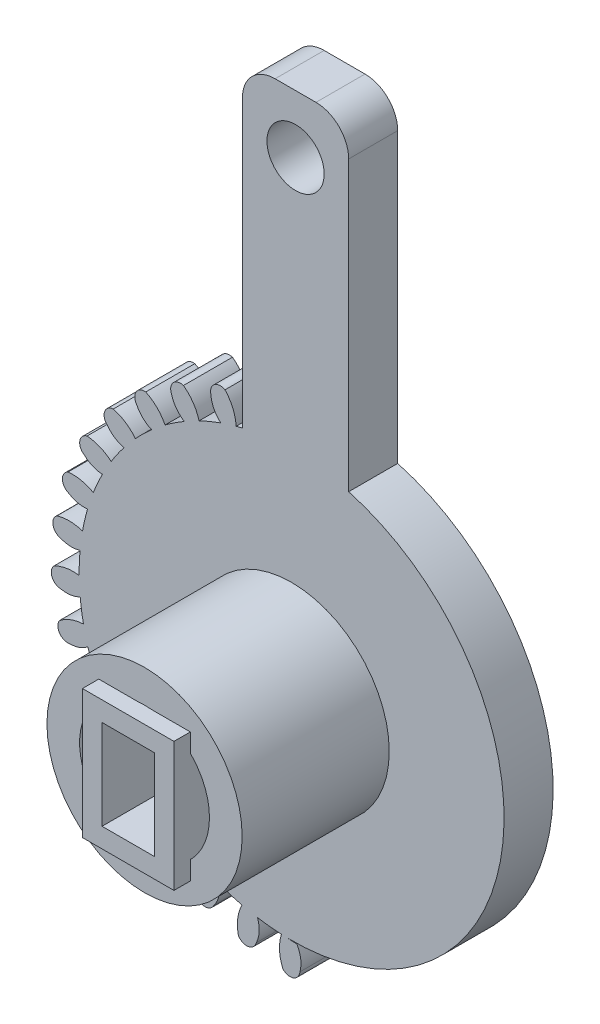
SolidWorks part; units mm, degrees
ref_plane "Front Plane" through (0, 0, 0) normal (0, 0, 1) x (1, 0, 0)
ref_plane "Top Plane" through (0, 0, 0) normal (0, 1, 0) x (1, 0, 0)
ref_plane "Right Plane" through (0, 0, 0) normal (1, 0, 0) x (0, 0, -1)
ref_plane "Plane1" through (0, 0, 5) normal (0, 0, 1) x (1, 0, 0)
ref_plane "Plane2" through (0, 0, 11) normal (0, 0, 1) x (1, 0, 0)
ref_plane "Plane3" through (0, 0, 3) normal (0, 0, 1) x (1, 0, 0)
sketch "Sketch1" plane through (0, 0, 5) normal (0, 0, 1) x (1, 0, 0)
  circle A0 centre (0, 20.9252) radius 3.9726
  circle A1 centre (0, 20.9252) radius 5
  dimension "D1" = 10
sketch "Sketch3" plane through (0, 0, 11) normal (0, 0, 1) x (1, 0, 0)
  line L0 (-3.9726, 20.9252) -> (15.3734, 20.9252) construction
  line L1 (0, 24.8978) -> (0, 8.7425) construction
  line L3 (-1.6, 23.6752) -> (1.6, 23.6752)
  line L4 (-1.6, 23.6752) -> (-1.6, 18.1752)
  line L5 (-1.6, 18.1752) -> (1.6, 18.1752)
  line L6 (1.6, 23.6752) -> (1.6, 18.1752)
  dimension "D1" = 3.2
  dimension "D2" = 5.5
  dimension "D3" = 1.6
  dimension "D4" = 2.75
extrude "Boss-Extrude1" add sketch "Sketch1" along normal blind 10 contours A0
shell "Shell1" thickness 2 removed face at (3.9726, 20.9252, 15) outward yes
extrude "Boss-Extrude2" add sketch "Sketch3" along normal blind 5 separate body
shell "Shell2" thickness 1.2 removed face at (0, 20.9252, 16) outward yes
sketch "Sketch7" plane through (0, 0, 3) normal (0, 0, -1) x (-1, 0, 0)
  line L0 (0, 14.9526) -> (0, 35.2199) construction
  line L1 (5.9726, 20.9252) -> (-26.894, 20.9252) construction
  circle A0 centre (0, 20.9252) radius 5.9726 construction
sketch "Sketch5" plane through (0, 0, 3) normal (0, 0, 1) x (1, 0, 0)
  line L1 (0, 14.9526) -> (0, 35.2199) construction
  line L2 (-5.9726, 20.9252) -> (26.894, 20.9252) construction
  circle A0 centre (0, 20.9252) radius 13
extrude "Boss-Extrude3" add sketch "Sketch5" along normal blind 3 contours A0
sketch "Sketch6" plane through (0, 0, 3) normal (0, 0, 1) x (1, 0, 0)
  line L1 (-3.01, 33.0817) -> (3.49, 33.0817)
  line L2 (-3.01, 33.0817) -> (-3.01, 53.0817)
  line L3 (-3.01, 53.0817) -> (3.49, 53.0817)
  line L4 (3.49, 33.0817) -> (3.49, 53.0817)
  point P4 (-3.01, 33.0817)
  dimension "D1" = 20
  dimension "D2" = 6.5
extrude "Boss-Extrude4" add sketch "Sketch6" along normal up to surface (3 mm away) up to face at (5.9726, 20.9252, 6)
sketch "Sketch8" plane through (0, 0, 3) normal (0, 0, 1) x (1, 0, 0)
  line L0 (-4.296, 33.1462) -> (-3.39, 33.4105)
  line L1 (0.24, 53.0817) -> (0.24, -3.388) construction
  line L2 (3.49, 53.0817) -> (-3.01, 53.0817) construction
  line L3 (13, 20.9252) -> (-7.0281, 20.9252) construction
  line L4 (-6.4797, 32.0955) -> (-5.6382, 32.5229)
  line L5 (-8.4311, 30.6587) -> (-7.6833, 31.2345)
  line L6 (-10.0829, 28.8855) -> (-9.4546, 29.5898)
  line L7 (-11.3779, 26.8373) -> (-10.8908, 27.6456)
  line L8 (-12.2715, 24.5847) -> (-11.9424, 25.4693)
  line L9 (-12.7326, 22.2057) -> (-12.573, 23.1358)
  line L10 (-12.7455, 19.7824) -> (-12.7607, 20.726)
  line L11 (-12.3095, 17.3986) -> (-12.4992, 18.3231)
  line L12 (-11.4399, 15.1367) -> (-11.7974, 16.0101)
  line L13 (-10.1667, 13.0748) -> (-10.6797, 13.867)
  line L14 (-8.5338, 11.2842) -> (-9.1845, 11.9678)
  line L15 (-6.5977, 9.8268) -> (-7.3637, 10.3781)
  line L16 (-4.4253, 8.753) -> (-5.2801, 9.1529)
  line L17 (-2.0916, 8.0998) -> (-3.0057, 8.3346)
  line L18 (0.3226, 7.8899) -> (-0.6192, 7.9514)
  arc A0 (-3.39, 33.4105) -> (-4.0758, 35.0663) centre (-5.9543, 33.3183) ccw
  arc A1 (-5.6382, 32.5229) -> (-6.6186, 34.0231) centre (-8.1411, 31.9576) ccw
  arc A2 (-4.0758, 35.0663) -> (-4.9399, 34.3825) centre (-4.3614, 34.5393) ccw
  arc A3 (-4.9399, 34.3825) -> (-4.296, 33.1462) centre (-3.1926, 34.5068) ccw
  arc A4 (-3.01, 33.572) -> (3.49, 33.448) centre (0, 20.9252) ccw construction
  arc A5 (-6.6186, 34.0231) -> (-7.3413, 33.1912) centre (-6.8018, 33.4524) ccw
  arc A6 (-7.3413, 33.1912) -> (-6.4797, 32.0955) centre (-5.6471, 33.6368) ccw
  arc A7 (-7.6833, 31.2345) -> (-8.9245, 32.5273) centre (-10.0383, 30.2157) ccw
  arc A8 (-8.9245, 32.5273) -> (-9.4806, 31.576) centre (-8.9988, 31.9325) ccw
  arc A9 (-9.4806, 31.576) -> (-8.4311, 30.6587) centre (-7.8982, 32.3274) ccw
  arc A10 (-9.4546, 29.5898) -> (-10.9136, 30.6305) centre (-11.5804, 28.1527) ccw
  arc A11 (-10.9136, 30.6305) -> (-11.2841, 29.5927) centre (-10.8765, 30.0323) ccw
  arc A12 (-11.2841, 29.5927) -> (-10.0829, 28.8855) centre (-9.8681, 30.6241) ccw
  arc A13 (-10.8908, 27.6456) -> (-12.5173, 28.3983) centre (-12.7139, 25.8399) ccw
  arc A14 (-12.5173, 28.3983) -> (-12.6892, 27.3099) centre (-12.3701, 27.8173) ccw
  arc A15 (-12.6892, 27.3099) -> (-11.3779, 26.8373) centre (-11.4887, 28.5855) ccw
  arc A16 (-11.9424, 25.4693) -> (-13.6801, 25.9079) centre (-13.3997, 23.3573) ccw
  arc A17 (-13.6801, 25.9079) -> (-13.6476, 24.8064) centre (-13.4279, 25.3641) ccw
  arc A18 (-13.6476, 24.8064) -> (-12.2715, 24.5847) centre (-12.7039, 26.2823) ccw
  arc A19 (-12.573, 23.1358) -> (-14.3618, 23.2453) centre (-13.6142, 20.7907) ccw
  arc A20 (-14.3618, 23.2453) -> (-14.126, 22.1688) centre (-14.0133, 22.7576) ccw
  arc A21 (-14.126, 22.1688) -> (-12.7326, 22.2057) centre (-13.4718, 23.7938) ccw
  arc A22 (-12.7607, 20.726) -> (-14.5389, 20.5025) centre (-13.3499, 18.2286) ccw
  arc A23 (-14.5389, 20.5025) -> (-14.1079, 19.4883) centre (-14.1062, 20.0877) ccw
  arc A24 (-14.1079, 19.4883) -> (-12.7455, 19.7824) centre (-13.7658, 21.2063) ccw
  arc A25 (-12.4992, 18.3231) -> (-14.2053, 17.7743) centre (-12.616, 15.7598) ccw
  arc A26 (-14.2053, 17.7743) -> (-13.5941, 16.8574) centre (-13.7033, 17.4468) ccw
  arc A27 (-13.5941, 16.8574) -> (-12.3095, 17.3986) centre (-13.5758, 18.609) ccw
  arc A28 (-11.7974, 16.0101) -> (-13.3725, 15.155) centre (-11.4377, 13.4695) ccw
  arc A29 (-13.3725, 15.155) -> (-12.6021, 14.3671) centre (-12.8185, 14.926) ccw
  arc A30 (-12.6021, 14.3671) -> (-11.4399, 15.1367) centre (-12.9084, 16.0918) ccw
  arc A31 (-10.6797, 13.867) -> (-12.0692, 12.7351) centre (-9.8559, 11.4368) ccw
  arc A32 (-12.0692, 12.7351) -> (-11.1663, 12.1034) centre (-11.4825, 12.6126) ccw
  arc A33 (-11.1663, 12.1034) -> (-10.1667, 13.0748) centre (-11.7865, 13.7417) ccw
  arc A34 (-9.1845, 11.9678) -> (-10.3406, 10.5982) centre (-7.9252, 9.7321) ccw
  arc A35 (-10.3406, 10.5982) -> (-9.3363, 10.1446) centre (-9.7413, 10.5865) ccw
  arc A36 (-9.3363, 10.1446) -> (-8.5338, 11.2842) centre (-10.2491, 11.6397) ccw
  arc A37 (-7.3637, 10.3781) -> (-8.2463, 8.8183) centre (-5.7123, 8.4142) ccw
  arc A38 (-8.2463, 8.8183) -> (-7.1754, 8.5583) centre (-7.6552, 8.9177) ccw
  arc A39 (-7.1754, 8.5583) -> (-6.5977, 9.8268) centre (-8.3491, 9.8587) ccw
  arc A40 (-5.2801, 9.1529) -> (-5.8587, 7.4567) centre (-3.2937, 7.5286) ccw
  arc A41 (-5.8587, 7.4567) -> (-4.7582, 7.3995) centre (-5.2962, 7.6638) ccw
  arc A42 (-4.7582, 7.3995) -> (-4.4253, 8.753) centre (-6.1524, 8.4601) ccw
  arc A43 (-3.0057, 8.3346) -> (-3.2603, 6.5606) centre (-0.753, 7.106) ccw
  arc A44 (-3.2603, 6.5606) -> (-2.1683, 6.7081) centre (-2.7459, 6.8682) ccw
  arc A45 (-2.1683, 6.7081) -> (-2.0916, 8.0998) centre (-3.7347, 7.4923) ccw
  arc A46 (-0.6192, 7.9514) -> (-0.541, 6.1609) centre (1.822, 7.161) ccw
  arc A47 (-0.541, 6.1609) -> (0.5049, 6.508) centre (-0.0924, 6.5585) ccw
  arc A48 (0.5049, 6.508) -> (0.3226, 7.8899) centre (-1.1796, 6.9887) ccw
  point P26 (0.24, 20.9252)
  point P153 (0.24, 20.9252)
  dimension "D1" = 16
extrude "Boss-Extrude5" add sketch "Sketch8" along normal up to surface (3 mm away) up to face at (0.118, 36.9003, 6)
sketch "Sketch9" plane through (0, 0, 3) normal (0, 0, -1) x (-1, 0, 0)
  line L0 (-0.24, 53.0817) -> (-0.24, 49.0919) construction
  line L1 (-3.49, 53.0817) -> (3.01, 53.0817) construction
  circle A0 centre (-0.24, 49.5317) radius 1.75
  dimension "D1" = 3.55
extrude "Cut-Extrude1" cut sketch "Sketch9" against normal up to surface (3 mm away) up to face at (-8.1909, 20.6875, 6)
fillet "Fillet1" radius 2 2 edges at (3.49, 53.0817, 4.5) (-3.01, 53.0817, 4.5)
